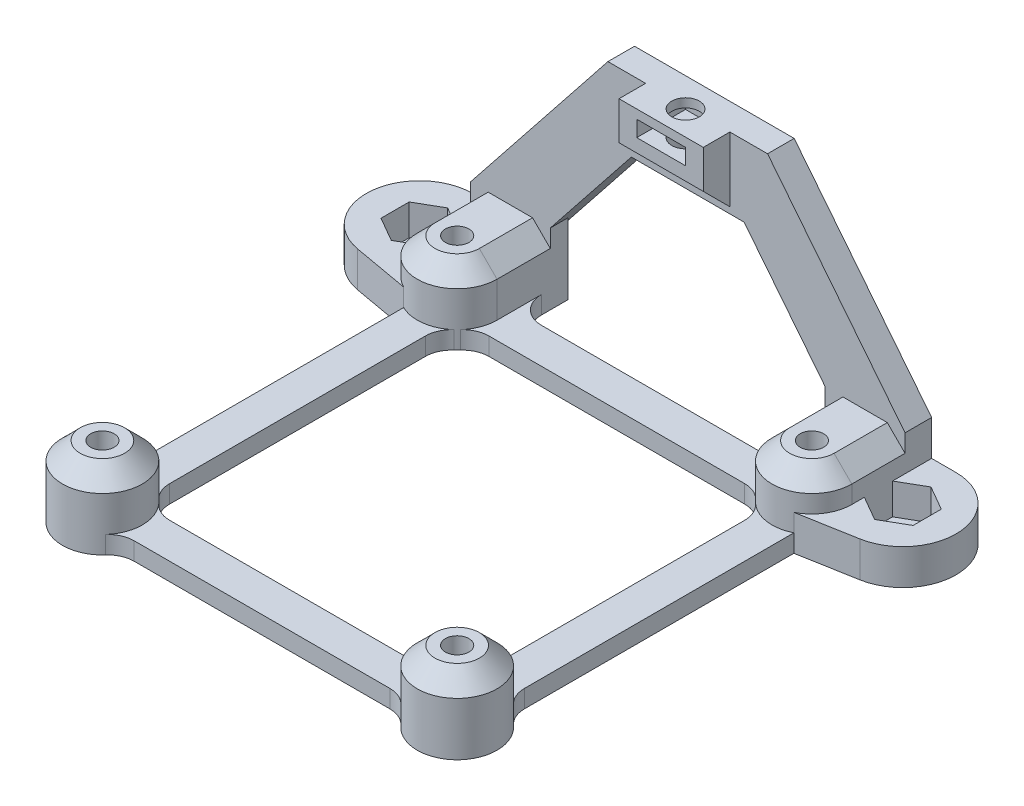
SolidWorks part; units mm, degrees
ref_plane "Front Plane" through (0, 0, 0) normal (0, 0, 1) x (1, 0, 0)
ref_plane "Top Plane" through (0, 0, 0) normal (0, 1, 0) x (1, 0, 0)
ref_plane "Right Plane" through (0, 0, 0) normal (1, 0, 0) x (0, 0, -1)
sketch "Sketch1" plane through (0, 0, 0) normal (0, 1, 0) x (1, 0, 0)
  line L0 (0, 0) -> (-49.6209, 0) construction
  line L1 (-24.5, -34.5) -> (-24.5, -25.5)
  line L2 (-20, -34.5) -> (20, -34.5) construction
  line L3 (-20, -34.5) -> (-20, -74.5) construction
  line L4 (-20, -74.5) -> (20, -74.5) construction
  line L5 (20, -34.5) -> (20, -74.5) construction
  line L6 (-24.5, -25.5) -> (-15.5, -25.5)
  line L7 (-15.5, -25.5) -> (-15.5, -34.5)
  line L8 (0, -34.5) -> (0, -74.5) construction
  line L9 (24.5, -34.5) -> (24.5, -25.5)
  line L10 (15.5, -25.5) -> (15.5, -34.5)
  line L11 (24.5, -25.5) -> (15.5, -25.5)
  circle A2 centre (20, -74.5) radius 4.5
  circle A3 centre (-20, -74.5) radius 4.5
  circle A4 centre (-20, -34.5) radius 1.325
  circle A5 centre (20, -34.5) radius 1.325
  circle A6 centre (-20, -74.5) radius 1.325
  circle A7 centre (20, -74.5) radius 1.325
  arc A8 (-24.5, -34.5) -> (-15.5, -34.5) centre (-20, -34.5) ccw
  arc A9 (24.5, -34.5) -> (15.5, -34.5) centre (20, -34.5) cw
  point P7 (0, -34.5)
  dimension "D1" = 9
  dimension "D2" = 2.65
  dimension "D4" = 9
  dimension "D3" = 40
  dimension "D5" = 25.5
extrude "Boss-Extrude1" add sketch "Sketch1" along normal blind 8
sketch "Sketch2" plane through (24.5, 0, 0) normal (1, 0, 0) x (0, 0, -1)
  line L0 (-25.5, 0) -> (-25.5, 27.5)
  line L2 (0, 27.5) -> (0, 0) construction
  line L3 (-25.5, 0) -> (-28.5, 0)
  line L4 (-28.5, 0) -> (-28.5, 27.5)
  line L7 (-28.5, 27.5) -> (-25.5, 27.5)
  line L8 (0, 27.5) -> (-25.5, 27.5) construction
  dimension "D1" = 3
  dimension "D2" = 27.5
extrude "Boss-Extrude2" add sketch "Sketch2" against normal up to surface (49 mm away) up to face at (-24.5, 4, 30)
sketch "Sketch3" plane through (0, 0, 28.5) normal (0, 0, 1) x (1, 0, 0)
  line L0 (-24.5, 8) -> (-9, 27.5)
  line L1 (-9, 27.5) -> (9, 27.5) construction
  line L3 (-24.5, 27.5) -> (24.5, 27.5) construction
  line L4 (-24.5, 27.5) -> (-9, 27.5)
  line L6 (9, 27.5) -> (24.5, 8)
  line L7 (24.5, 8) -> (24.5, 27.5)
  line L10 (-24.5, 27.5) -> (-24.5, 8)
  line L11 (-15.5, 8) -> (-15.5, 0)
  line L12 (-15.5, 0) -> (15.5, 0)
  line L13 (15.5, 0) -> (15.5, 8)
  line L14 (15.5, 8) -> (6.359, 19.5)
  line L15 (6.359, 19.5) -> (-6.359, 19.5)
  line L16 (-6.359, 19.5) -> (-15.5, 8)
  line L17 (24.5, 27.5) -> (9, 27.5)
  point P9 (0, 27.5)
  point P24 (0, 19.5)
  dimension "D1" = 18
  dimension "D2" = 8
extrude "Cut-Extrude1" cut sketch "Sketch3" against normal through all
sketch "Sketch4" plane through (0, 0, 0) normal (0, -1, 0) x (1, 0, 0)
  line L0 (-20, 34.5) -> (20, 34.5) construction
  line L1 (20, 34.5) -> (20, 74.5) construction
  line L2 (-20, 74.5) -> (20, 74.5) construction
  line L3 (-20, 34.5) -> (-20, 74.5) construction
  line L4 (-20, 34.5) -> (20, 34.5) construction
  line L5 (20, 34.5) -> (20, 74.5) construction
  line L6 (-20, 74.5) -> (20, 74.5) construction
  line L7 (-20, 34.5) -> (-20, 74.5) construction
  line L8 (-22, 76.5) -> (22, 76.5)
  line L9 (22, 32.5) -> (22, 76.5)
  line L10 (-22, 32.5) -> (22, 32.5)
  line L11 (-22, 32.5) -> (-22, 76.5)
  line L12 (-18, 72.5) -> (18, 72.5)
  line L13 (18, 36.5) -> (18, 72.5)
  line L14 (-18, 36.5) -> (18, 36.5)
  line L15 (-18, 36.5) -> (-18, 72.5)
  dimension "D1" = 2
  dimension "D2" = 2
extrude "Boss-Extrude3" add sketch "Sketch4" against normal blind 2
sketch "Sketch7" plane through (0, 27.5, 0) normal (0, 1, 0) x (1, 0, 0)
  line L0 (-9, -25.5) -> (9, -25.5) construction
  line L1 (-2.75, -26) -> (2.75, -26) construction
  line L2 (-2.75, -26) -> (-2.75, -31.5) construction
  line L3 (-2.75, -31.5) -> (2.75, -31.5) construction
  line L4 (2.75, -26) -> (2.75, -31.5) construction
  line L5 (-9, -28.5) -> (9, -28.5) construction
  line L6 (-4.75, -28.5) -> (4.75, -28.5)
  line L7 (-4.75, -28.5) -> (-4.75, -31.5)
  line L8 (-4.75, -31.5) -> (4.75, -31.5)
  line L9 (4.75, -28.5) -> (4.75, -31.5)
  point P4 (0, -26)
  point P14 (0, -28.5)
  dimension "D1" = 5.5
  dimension "D2" = 0.5
  dimension "D3" = 2
extrude "Boss-Extrude5" add sketch "Sketch7" against normal blind 4.3
sketch "Sketch8" plane through (0, 27.5, 0) normal (0, 1, 0) x (1, 0, 0)
  line L1 (-2.75, -26) -> (2.75, -26)
  line L2 (-2.75, -26) -> (-2.75, -31.5)
  line L3 (-2.75, -31.5) -> (2.75, -31.5)
  line L4 (2.75, -26) -> (2.75, -31.5)
extrude "Cut-Extrude3" cut sketch "Sketch8" against normal blind 1.8 from offset 1 offset against normal yes
chamfer "Chamfer3" distance 3 angle 45 1 edges at (0, 23.2, 28.5)
sketch "Sketch9" plane through (0, 27.5, 0) normal (0, 1, 0) x (1, 0, 0)
  line L0 (-2.75, -26) -> (-2.75, -31.5) construction
  line L1 (-2.75, -26) -> (2.75, -26) construction
  circle A0 centre (0, -28.75) radius 1.55
  point P5 (-2.75, -28.75)
  point P8 (0, -26)
  dimension "D1" = 3.1
extrude "Cut-Extrude4" cut sketch "Sketch9" against normal blind 5.4
sketch "Sketch10" plane through (0, 0, 0) normal (0, -1, 0) x (1, 0, 0)
  line L0 (-24.5, 25.5) -> (-27.25, 25.5)
  line L1 (-27.25, 28.3246) -> (-24.5, 29.9123)
  line L2 (-24.5, 29.9123) -> (-24.5, 33.0877)
  line L3 (-24.5, 33.0877) -> (-27.25, 34.6754)
  line L4 (-27.25, 34.6754) -> (-30, 33.0877)
  line L5 (-30, 33.0877) -> (-30, 29.9123)
  line L6 (-30, 29.9123) -> (-27.25, 28.3246)
  line L7 (-24.5, 25.5) -> (-24.5, 34.5) construction
  line L8 (-22, 38.5311) -> (-28.3036, 37.4068)
  line L10 (-22, 38.5311) -> (-22, 25.5)
  line L11 (-15.5, 25.5) -> (-24.5, 25.5) construction
  line L12 (-22, 25.5) -> (-24.5, 25.5)
  circle A0 centre (-27.25, 31.5) radius 2.75 construction
  arc A2 (-27.25, 25.5) -> (-28.3036, 37.4068) centre (-27.25, 31.5) cw
  dimension "D2" = 6
  dimension "D1" = 5.5
extrude "Boss-Extrude6" add sketch "Sketch10" against normal blind 4
sketch "Sketch11" plane through (0, 0, 0) normal (0, -1, 0) x (1, 0, 0)
  line L1 (-30, 33.0877) -> (-30, 29.9123) construction
  line L2 (-30, 29.9123) -> (-27.25, 28.3246) construction
  line L3 (-27.25, 28.3246) -> (-24.5, 29.9123) construction
  line L4 (-24.5, 29.9123) -> (-24.5, 33.0877) construction
  line L5 (-24.5, 33.0877) -> (-27.25, 34.6754) construction
  line L6 (-27.25, 34.6754) -> (-30, 33.0877) construction
  line L7 (-30, 33.0877) -> (-30, 29.9123)
  line L8 (-30, 29.9123) -> (-27.25, 28.3246)
  line L9 (-27.25, 28.3246) -> (-24.5, 29.9123)
  line L10 (-24.5, 29.9123) -> (-24.5, 33.0877)
  line L11 (-24.5, 33.0877) -> (-27.25, 34.6754)
  line L12 (-27.25, 34.6754) -> (-30, 33.0877)
  circle A1 centre (-27.25, 31.5) radius 1.5
  dimension "D1" = 3
extrude "Boss-Extrude7" add sketch "Sketch11" against normal blind 0.5
mirror "Mirror1" about plane through (0, 0, 0) normal (1, 0, 0) of "Boss-Extrude7", "Boss-Extrude6"
fillet "Fillet2" radius 3 14 edges at (-15.5, 1, 32.5) (15.5, 1, 32.5) (-22, 1, 70.4689) (22, 1, 70.4689) (15.9689, 1, 76.5) (-15.9689, 1, 76.5) (18, 1, 70.4689) (15.9689, 1, 72.5) (18, 1, 38.5311) (15.9689, 1, 36.5) (-18, 1, 70.4689) (-15.9689, 1, 72.5) (-15.9689, 1, 36.5) (-18, 1, 38.5311)
chamfer "Chamfer4" distance 1 angle 45 2 edges at (15.5, 4, 25.5) (-15.5, 4, 25.5)
chamfer "Chamfer5" distance 2 angle 45 8 edges at (20, 8, 79) (15.5, 8, 31.5) (24.5, 8, 31.5) (20, 8, 39) (-24.5, 8, 31.5) (-15.5, 8, 31.5) (-20, 8, 39) (-20, 8, 79)
